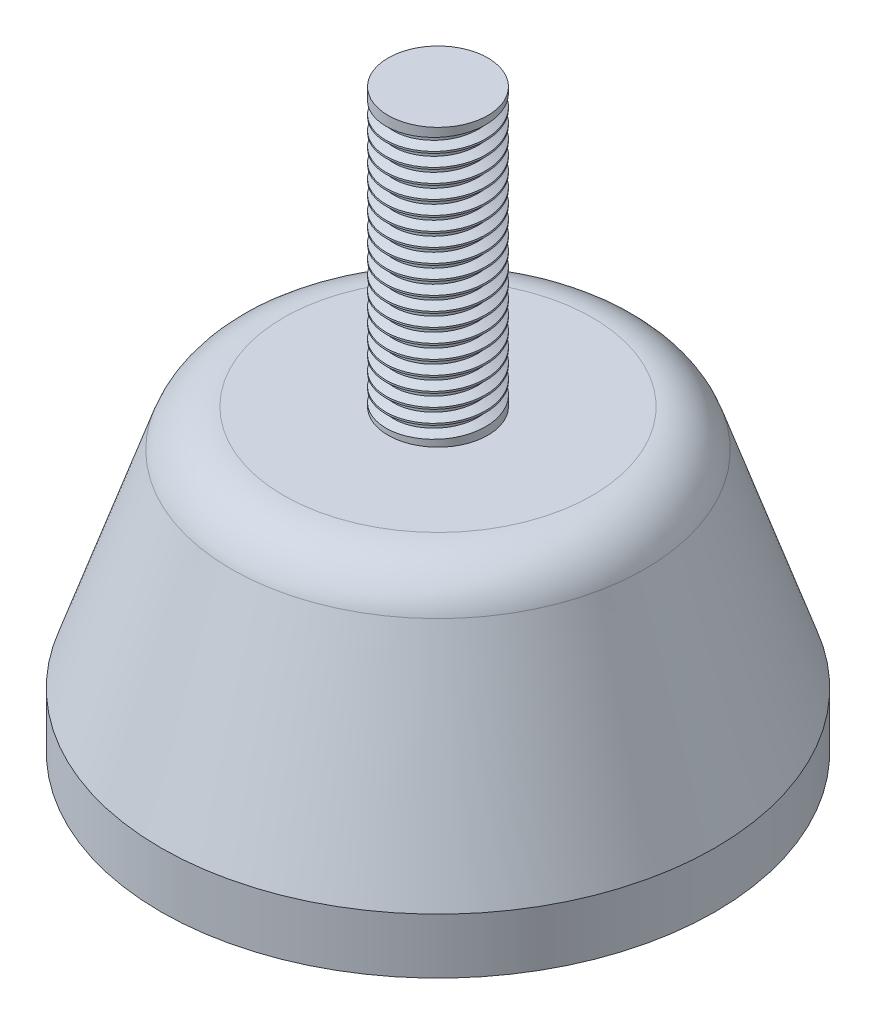
SolidWorks part; units mm, degrees
ref_plane "Alzado" through (0, 0, 0) normal (0, 0, 1) x (1, 0, 0)
ref_plane "Planta" through (0, 0, 0) normal (0, 1, 0) x (1, 0, 0)
ref_plane "Vista lateral" through (0, 0, 0) normal (1, 0, 0) x (0, 0, -1)
sketch "Croquis1" plane through (0, 0, 0) normal (0, 0, 1) x (1, 0, 0)
  line L0 (0, 0) -> (-25, 0)
  line L1 (-25, 0) -> (-25, 5)
  line L2 (-25, 5) -> (-18.6545, 23.6134)
  line L3 (-13.922, 27) -> (0, 27)
  line L4 (0, 27) -> (0, 0)
  arc A0 (-18.6545, 23.6134) -> (-13.922, 27) centre (-13.922, 22) cw
  point P8 (-17.5, 27)
  dimension "D5" = 5
  dimension "D1" = 25
  dimension "D2" = 5
  dimension "D3" = 22
  dimension "D4" = 17.5
revolve "Revolución1" add sketch "Croquis1" angle 360 about L4
sketch "Croquis2" plane through (0, 27, 0) normal (0, 1, 0) x (1, 0, 0)
  circle A0 centre (0, 0) radius 4.5
  dimension "D1" = 9
extrude "Saliente-Extruir1" add sketch "Croquis2" along normal blind 25 separate body
thread "Rosca1" pitch 1.25 method cut profile "Perfil de rosca1" start angle 0, offset 0, length 0, pitch 1.25, diameter 9
ref_plane "Plano1" through (-4.5, 52, 0) normal (0, 0, 1) x (-1, 0, 0)
sketch "Perfil de rosca1" plane through (-4.5, 52, 0) normal (0, 0, 1) x (-1, 0, 0)
  line L0 (0, 0) -> (0, 1.25) construction
  line L11 (0, 0) -> (0, 1.0937)
  line L12 (0, 1.0937) -> (-0.6766, 0.7031)
  line L13 (-0.6766, 0.7031) -> (-0.6766, 0.3906)
  line L15 (-0.6766, 0.3906) -> (0, 0)
  line L17 (-0.6766, 0.5469) -> (0, 0.5469) construction
  point P2 (0, 0)
  dimension "Pitch" = 1.25
  dimension "Profile_Angle" = 60
  dimension "Profile_Land" = 0.3125
  dimension "Profile_Height" = 0.6766
